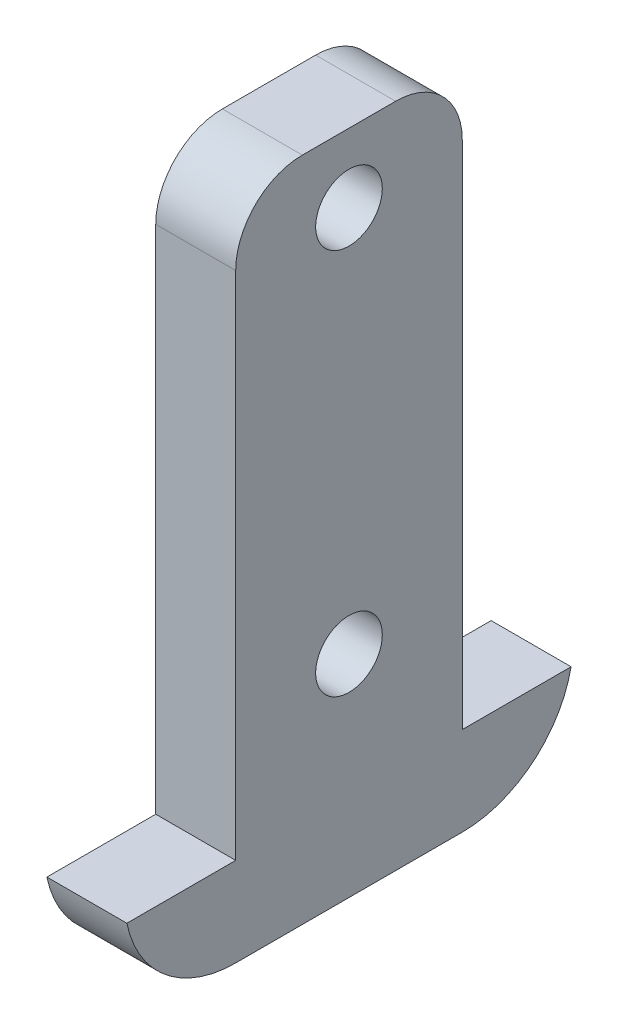
SolidWorks part; units mm, degrees
ref_plane "Plano frontal" through (0, 0, 0) normal (0, 0, 1) x (1, 0, 0)
ref_plane "Plano superior" through (0, 0, 0) normal (0, 1, 0) x (1, 0, 0)
ref_plane "Plano direito" through (0, 0, 0) normal (1, 0, 0) x (0, 0, -1)
sketch "Esboço1" plane through (0, 0, 0) normal (1, 0, 0) x (0, 0, -1)
  line L0 (0, 0) -> (20, 0)
  line L1 (20, 0) -> (20, 4)
  line L2 (20, 4) -> (15.1, 4)
  line L3 (15.1, 4) -> (15.1, 30)
  line L4 (15.1, 30) -> (4.9, 30)
  line L5 (4.9, 30) -> (4.9, 4)
  line L6 (4.9, 4) -> (0, 4)
  line L7 (0, 4) -> (0, 0)
  circle A0 centre (10, 26.9) radius 1.5
  circle A1 centre (10, 9.5) radius 1.5
  point P8 (15.1, 17)
  dimension "D5" = 3
  dimension "D7" = 3
  dimension "D1" = 10.2
  dimension "D2" = 26
  dimension "D3" = 4
  dimension "D4" = 20
  dimension "D6" = 5.5
  dimension "D8" = 17.4
  dimension "D9" = 5.1
extrude "Ressalto-extrusão1" add sketch "Esboço1" along normal blind 3.6
fillet "Filete1" radius 3 2 edges at (1.8, 30, -15.1) (1.8, 30, -4.9)
fillet "Filete2" radius 5 2 edges at (1.8, 0, 0) (1.8, 0, -20)
